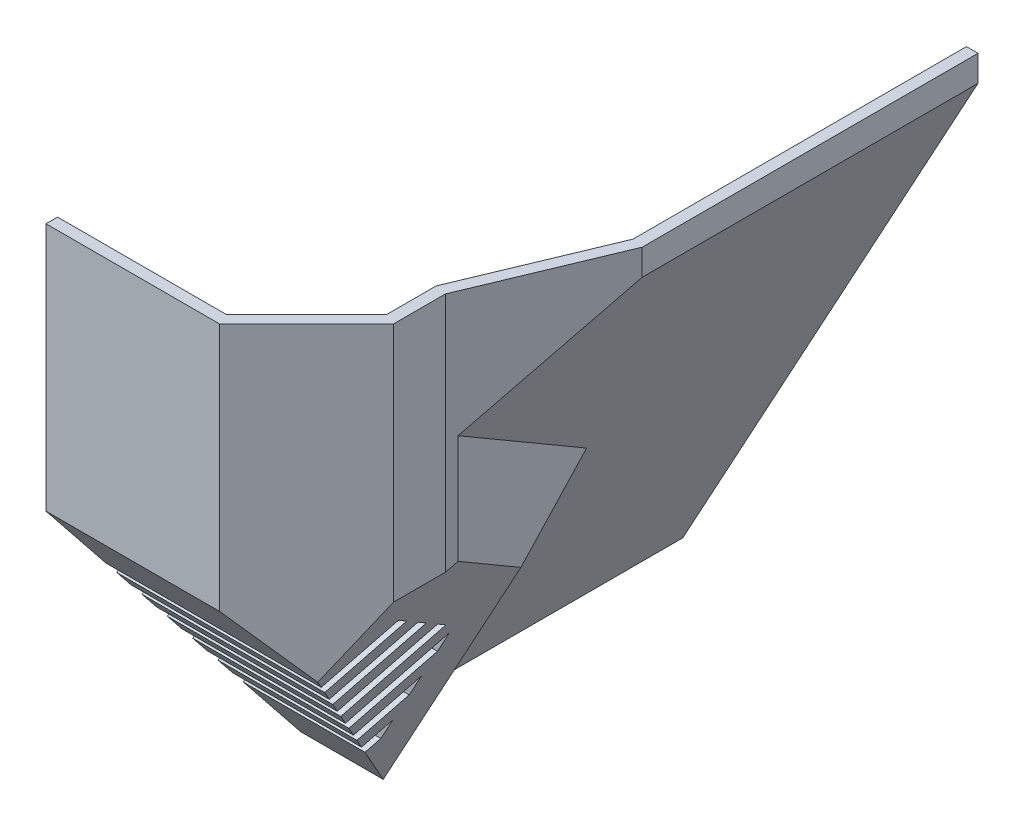
SolidWorks part; units mm, degrees
ref_plane "Plan de face" through (0, 0, 0) normal (0, 0, 1) x (1, 0, 0)
ref_plane "Plan de dessus" through (0, 0, 0) normal (0, 1, 0) x (1, 0, 0)
ref_plane "Plan de droite" through (0, 0, 0) normal (1, 0, 0) x (0, 0, -1)
sketch "Esquisse1" plane through (0, 0, 0) normal (0, 0, 1) x (1, 0, 0)
  line L1 (0, 0) -> (275, 0)
  line L2 (0, 0) -> (0, 490)
  line L3 (0, 490) -> (275, 490)
  line L4 (275, 0) -> (275, 490)
  dimension "D1" = 275
  dimension "D2" = 490
extrude "Boss.-Extru.1" add sketch "Esquisse1" along normal blind 550
sketch "Esquisse2" plane through (0, 490, 0) normal (0, 1, 0) x (1, 0, 0)
  line L0 (275, -530) -> (125, -530)
  line L1 (275, -550) -> (275, 0) construction
  line L2 (125, -530) -> (50, -455)
  line L3 (0, -550) -> (0, 0) construction
  line L4 (0, -290) -> (0, -530) construction
  line L5 (0, -530) -> (125, -530) construction
  line L6 (275, -530) -> (275, -619.0675)
  line L7 (275, -619.0675) -> (-74.3807, -619.0675)
  line L8 (-74.3807, -619.0675) -> (-74.3807, -290)
  line L9 (-74.3807, -290) -> (0, -290)
  line L10 (275, -550) -> (0, -550) construction
  line L11 (50, -455) -> (50, -410)
  line L12 (50, -410) -> (0, -290)
  line L13 (125, -530) -> (125, -455) construction
  line L14 (125, -455) -> (50, -455) construction
  line L15 (50, -410) -> (0, -410) construction
  dimension "D1" = 20
  dimension "D2" = 150
  dimension "D3" = 45
  dimension "D4" = 120
  dimension "D5" = 120
  dimension "D6" = 50
extrude "Enlèv. mat.-Extru.1" cut sketch "Esquisse2" against normal through all
sketch "Esquisse3" plane through (275, 0, 0) normal (1, 0, 0) x (0, 0, -1)
  line L0 (-310, 0) -> (-530, 275)
  line L1 (-530, 0) -> (0, 0) construction
  line L2 (-530, 0) -> (-530, 490) construction
  line L3 (-530, 275) -> (-530, 0)
  line L4 (-530, 0) -> (-310, 0)
  line L5 (-530, 0) -> (-510, 0) construction
  line L6 (-510, 0) -> (-510, 250) construction
  line L7 (-510, 250) -> (-530, 275) construction
  dimension "D1" = 200
  dimension "D2" = 250
  dimension "D3" = 220
extrude "Enlèv. mat.-Extru.2" cut sketch "Esquisse3" against normal through all
sketch "Esquisse4" plane through (0, 0, 0) normal (0, 0, -1) x (-1, 0, 0)
  line L0 (-255, 0) -> (0, 0)
  line L1 (0, 0) -> (-275, 0) construction
  line L2 (0, 0) -> (45, 0) construction
  line L3 (45, 0) -> (45, 550) construction
  line L4 (45, 550) -> (0, 467.5) construction
  line L5 (0, 490) -> (0, 0) construction
  line L6 (0, 467.5) -> (-255, 0)
  line L7 (0, 467.5) -> (0, 0)
  dimension "D1" = 300
  dimension "D2" = 550
  dimension "D3" = 255
extrude "Enlèv. mat.-Extru.3" cut sketch "Esquisse4" against normal blind 310
chamfer "Chanfrein1" distance 100 angle 45 1 edges at (8.3333, 226.1111, 310) first distance on face at (19.4444, 337.4537, 336.6667)
chamfer "Chanfrein2" distance 45 angle 65 1 edges at (169.902, 156.0131, 310) first distance on face at (141.5359, 104.0087, 310)
sketch "Esquisse6" plane through (0, 0, 310) normal (0, 0, -1) x (-1, 0, 0)
  line L0 (-84.8039, 0) -> (-203.7411, 0)
  line L1 (-203.7411, 0) -> (-84.8039, 218.0514)
  line L2 (-84.8039, 218.0514) -> (-4.9032, 364.5361)
  line L3 (-4.9032, 364.5361) -> (-4.9032, 0)
  line L4 (-4.9032, 0) -> (-84.8039, 0)
extrude "Enlèv. mat.-Extru.5" cut sketch "Esquisse6" against normal blind 550
shell "Coque1" thickness 10
sketch "Esquisse7" plane through (275, 0, 0) normal (1, 0, 0) x (0, 0, -1)
  line L0 (-478.2594, 210.3242) -> (-431.8905, 247.4194) construction
  line L1 (-310, 0) -> (-530, 275) construction
  line L2 (-431.8905, 247.4194) -> (-350, 185.6001) construction
  line L3 (-350, 185.6001) -> (-350, 50) construction
  line L4 (-350, 50) -> (-478.2594, 210.3242) construction
  line L5 (-310, 218.0514) -> (-310, 0) construction
  line L6 (-431.8905, 247.4194) -> (-478.2594, 210.3242)
  line L7 (-478.2594, 210.3242) -> (-468.889, 198.6112)
  line L8 (-402.3077, 287.7347) -> (-310, 218.0514) construction
  line L9 (-487.6298, 222.0373) -> (-310, 0) construction
  line L10 (-468.889, 198.6112) -> (-419.5364, 238.0933)
  line L11 (-431.8905, 247.4194) -> (-419.5364, 238.0933)
  line L12 (-456.3951, 182.9938) -> (-355.4275, 263.7679) construction
  line L13 (-447.0246, 171.2808) -> (-346.0571, 252.0548) construction
  line L14 (-355.4275, 263.7679) -> (-346.0571, 252.0548) construction
  line L15 (-425.1603, 143.9504) -> (-324.1928, 224.7244) construction
  line L16 (-434.5307, 155.6634) -> (-333.5632, 236.4374) construction
  line L17 (-403.296, 116.62) -> (-302.3285, 197.394) construction
  line L18 (-412.6664, 128.333) -> (-311.6989, 209.107) construction
  line L19 (-381.4317, 89.2896) -> (-280.4641, 170.0636) construction
  line L20 (-390.8021, 101.0026) -> (-289.8346, 181.7766) construction
  line L21 (-359.5673, 61.9592) -> (-258.5998, 142.7332) construction
  line L22 (-368.9378, 73.6722) -> (-267.9702, 154.4462) construction
  line L23 (-456.3951, 182.9938) -> (-447.0246, 171.2808)
  line L24 (-447.0246, 171.2808) -> (-390.7102, 216.3323)
  line L25 (-390.7102, 216.3323) -> (-403.0643, 225.6585)
  line L26 (-403.0643, 225.6585) -> (-456.3951, 182.9938)
  line L27 (-434.5307, 155.6634) -> (-425.1603, 143.9504)
  line L28 (-425.1603, 143.9504) -> (-361.884, 194.5714)
  line L29 (-361.884, 194.5714) -> (-374.2381, 203.8975)
  line L30 (-374.2381, 203.8975) -> (-434.5307, 155.6634)
  line L31 (-434.5307, 155.6634) -> (-412.6664, 128.333)
  line L32 (-412.6664, 128.333) -> (-403.296, 116.62)
  line L33 (-403.296, 116.62) -> (-350, 159.2568)
  line L34 (-350, 159.2568) -> (-350, 178.4661)
  line L35 (-350, 178.4661) -> (-412.6664, 128.333)
  line L36 (-390.8021, 101.0026) -> (-381.4317, 89.2896)
  line L37 (-381.4317, 89.2896) -> (-350, 114.4349)
  line L38 (-350, 114.4349) -> (-350, 133.6443)
  line L39 (-350, 133.6443) -> (-390.8021, 101.0026)
  line L40 (-368.9378, 73.6722) -> (-359.5673, 61.9592)
  line L41 (-359.5673, 61.9592) -> (-350, 69.613)
  line L42 (-350, 69.613) -> (-350, 88.8224)
  line L43 (-350, 88.8224) -> (-368.9378, 73.6722)
  line M12 (-530, 275) -> (-310, 0)
  dimension "D1" = 50
  dimension "D2" = 40
  dimension "D3" = 15
  dimension "D4" = 15
  dimension "D5" = 20
  dimension "D6" = 15
  dimension "D8" = 20
  dimension "D7" = 5
extrude "Enlèv. mat.-Extru.6" cut sketch "Esquisse7" against normal blind 550 contours L34 L35 L33 M12 | L38 L39 L37 M12 | L42 L43 L41 M12 | L29 L30 L28 M12 | L25 L26 L24 M12 | L11 L6 L10 M12 region at (275, 223.5574, 449.5874) region at (275, 74.3638, 357.383) region at (275, 109.9271, 368.1597) region at (275, 145.8772, 379.0537) region at (275, 174.4784, 398.9096) region at (275, 199.0186, 424.2493)
sketch "Esquisse8" plane through (275, 0, 0) normal (1, 0, 0) x (0, 0, -1)
  line L0 (-520, 480) -> (-520, 278.5078)
  line L1 (-520, 278.5078) -> (-305.1938, 10)
  line L2 (-305.1938, 10) -> (0, 10)
  line L3 (0, 0) -> (0, 490) construction
  line L4 (0, 10) -> (0, 490)
  line L5 (0, 490) -> (-520, 490)
  line L6 (-530, 490) -> (0, 490) construction
  line L7 (-520, 490) -> (-520, 480)
extrude "Enlèv. mat.-Extru.7" cut sketch "Esquisse8" against normal blind 10
sketch "Esquisse9" plane through (0, 0, 0) normal (0, 0, -1) x (-1, 0, 0)
  line L0 (-10, 470.0499) -> (-10, 490)
  line L1 (-265, 490) -> (0, 490) construction
  line L2 (-10, 490) -> (-275, 490)
  line L3 (-275, 490) -> (-275, 10)
  line L4 (-275, 10) -> (-260.9363, 10)
  line L5 (-260.9363, 10) -> (-10, 470.0499)
extrude "Enlèv. mat.-Extru.8" cut sketch "Esquisse9" against normal blind 10
sketch "Esquisse10" plane through (0, 490, 0) normal (0, 1, 0) x (1, 0, 0)
  line L0 (265, -10) -> (10, -10)
  line L1 (10, -10) -> (10, -288)
  line L2 (10, -288) -> (60, -408)
  line L3 (60, -408) -> (60, -450.8579)
  line L4 (60, -450.8579) -> (129.1421, -520)
  line L5 (129.1421, -520) -> (265, -520)
  line L6 (265, -520) -> (265, -10)
extrude "Enlèv. mat.-Extru.9" cut sketch "Esquisse10" against normal blind 10
mirror "Symétrie1" about plane through (275, 0, 550) normal (-1, 0, 0) of bodies 110
sketch "Esquisse11" plane through (0, 490, 0) normal (0, 1, 0) x (1, 0, 0)
  line L0 (425, -530) -> (125, -530) construction
  line L1 (275, -530) -> (-227.378, -530)
  line L2 (275, -530) -> (275, 111.869)
  line L3 (275, 111.869) -> (-227.378, 111.869)
  line L4 (-227.378, -530) -> (-227.378, 111.869)
extrude "Enlèv. mat.-Extru.10" cut sketch "Esquisse11" against normal through all
